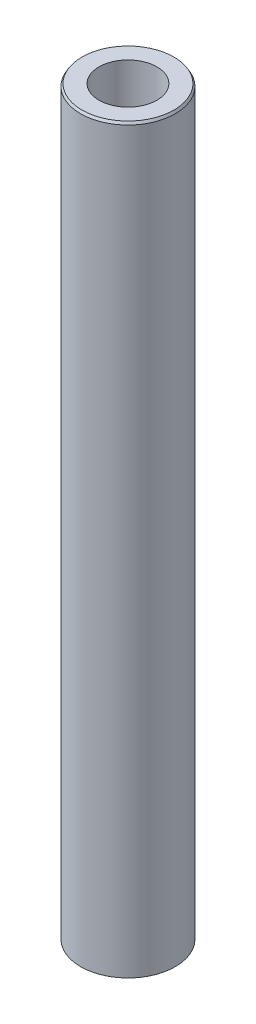
SolidWorks part; units mm, degrees
ref_plane "Front Plane" through (0, 0, 0) normal (0, 0, 1) x (1, 0, 0)
ref_plane "Top Plane" through (0, 0, 0) normal (0, 1, 0) x (1, 0, 0)
ref_plane "Right Plane" through (0, 0, 0) normal (1, 0, 0) x (0, 0, -1)
sketch "Sketch1" plane through (0, 0, 0) normal (0, 1, 0) x (1, 0, 0)
  circle A0 centre (0, 0) radius 22.5
  dimension "SHAFT_OD" = 45
extrude "Boss-Extrude1" add sketch "Sketch1" along normal blind 352.5295
sketch "Sketch2" plane through (0, 0, 0) normal (0, 1, 0) x (1, 0, 0)
  circle A0 centre (0, 0) radius 13.7466
  dimension "BORE_D" = 27.4933
extrude "Cut-Extrude1" cut sketch "Sketch2" along normal through all
chamfer "Chamfer1" distance 1.1717 angle 30 2 edges at (0, 352.5295, 22.5) (0, 0, 22.5) first distance on face at (0, 352.5295, 22.5) first distance on face at (0, 0, 13.7466)
